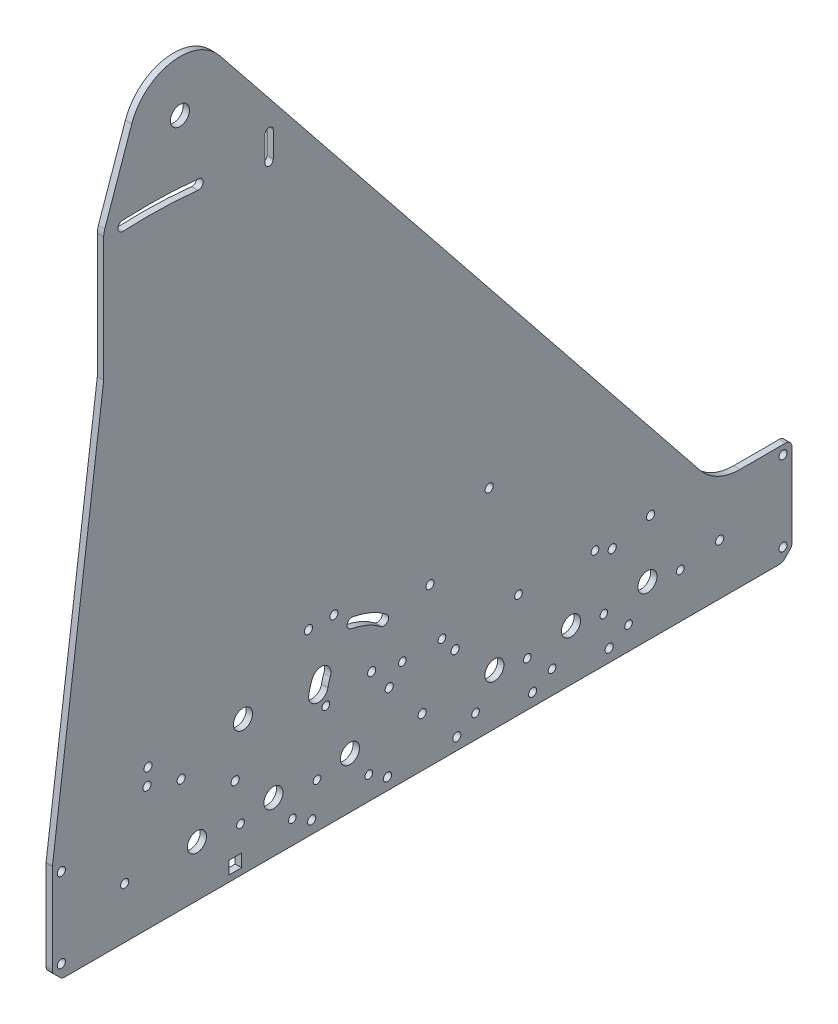
SolidWorks part; units mm, degrees
ref_plane "Front Plane" through (0, 0, 0) normal (0, 0, 1) x (1, 0, 0)
ref_plane "Top Plane" through (0, 0, 0) normal (0, 1, 0) x (1, 0, 0)
ref_plane "Right Plane" through (0, 0, 0) normal (1, 0, 0) x (0, 0, -1)
sketch "Sketch1" plane through (0, 0, 0) normal (1, 0, 0) x (0, 0, -1)
  line L0 (-184.15, -24.6062) -> (184.15, -24.6062)
  line L1 (184.15, -24.6062) -> (184.15, 26.1938)
  line L2 (184.15, 26.1938) -> (146.05, 26.1937)
  line L5 (-145.839, 321.5609) -> (-184.15, 26.1938)
  line L6 (-184.15, 26.1938) -> (-184.15, -24.6062)
  line L7 (-184.15, 350.0437) -> (184.15, 350.0437) construction
  line L9 (146.05, 26.1937) -> (-100.8314, 334.1803)
  arc A0 (-100.8314, 334.1803) -> (-145.839, 321.5609) centre (-120.65, 318.2937) ccw
  point P8 (0, -24.6062)
  dimension "D1" = 368.3
  dimension "D7" = 25.4
  dimension "D2" = 50.8
  dimension "D3" = 38.1
  dimension "D4" = 24.6062
  dimension "D5" = 374.65
  dimension "D6" = 304.8
  dimension "D8" = 342.9
extrude "Boss-Extrude1" add sketch "Sketch1" along normal blind 3.175
chamfer "Chamfer1" distance 4.7625 angle 45 2 edges at (1.5875, -24.6062, 184.15) (1.5875, -24.6062, -184.15)
fillet "Fillet1" radius 25.4 1 edges at (1.5875, 26.1937, -146.05)
fillet "Fillet2" radius 3.175 2 edges at (1.5875, 26.1938, 184.15) (1.5875, 26.1938, -184.15)
fillet "Fillet3" radius 3.175 4 edges at (1.5875, -19.8438, -184.15) (1.5875, -24.6062, -179.3875) (1.5875, -19.8437, 184.15) (1.5875, -24.6062, 179.3875)
sketch "Sketch30" plane through (3.175, 0, 0) normal (1, 0, 0) x (0, 0, -1)
  circle A8 centre (-89.211, 42.2593) radius 4.7625
  circle A9 centre (-25.1593, 30.6938) radius 2.032
  arc A10 (-51.7173, 35.4892) -> (-50.2741, 40.5715) centre (-25.1593, 30.6938) cw construction
  arc A11 (-54.7652, 42.3379) -> (-56.4665, 36.3468) centre (-25.1593, 30.6938) ccw
  arc A12 (-45.783, 38.8051) -> (-46.9681, 34.6317) centre (-25.1593, 30.6938) ccw
  arc A13 (-45.783, 38.8051) -> (-54.7652, 42.3379) centre (-50.2741, 40.5715) ccw
  arc A14 (-56.4665, 36.3468) -> (-46.9681, 34.6317) centre (-51.7173, 35.4892) ccw
  arc A15 (-34.9881, 56.6661) -> (-19.1131, 49.8125) centre (-41.7582, 19.1724) cw construction
  arc A16 (-17.6789, 51.753) -> (-34.5594, 59.0407) centre (-41.7582, 19.1724) ccw
  arc A17 (-20.5473, 47.8719) -> (-35.4169, 54.2915) centre (-41.7582, 19.1724) ccw
  arc A18 (-20.5473, 47.8719) -> (-17.6789, 51.753) centre (-19.1131, 49.8125) ccw
  arc A19 (-34.5594, 59.0407) -> (-35.4169, 54.2915) centre (-34.9881, 56.6661) ccw
  arc A20 (-19.1131, 49.8125) -> (-34.9881, 56.6661) centre (-41.7582, 19.1724) ccw construction
  circle A21 centre (94.6345, 23.8125) radius 2.032
  circle A22 centre (-56.6241, 64.5541) radius 2.032
  circle A23 centre (-43.9241, 64.5541) radius 2.032
  circle A24 centre (-56.6241, 64.5541) radius 1.905 construction
  circle A25 centre (-43.9241, 64.5541) radius 1.905 construction
  point P7 (-51.1204, 38.0658)
  point P19 (-26.6567, 54.1518)
  dimension "D2" = 9.652
  dimension "D4" = 4.064
  dimension "D1" = 4.064
  dimension ".375" = 9.525
  dimension "D3" = 4.826
extrude "Cut-Extrude9" cut sketch "Sketch30" against normal through all
sketch "Sketch16" plane through (3.175, 0, 0) normal (1, 0, 0) x (0, 0, -1)
  circle A0 centre (112.1746, 0.7937) radius 4.7625
  circle A1 centre (74.0746, 0.7937) radius 4.7625
  circle A2 centre (35.9746, 0.7937) radius 4.7625
  circle A3 centre (-35.9746, 0.7938) radius 4.7625
  circle A4 centre (-74.0746, 0.7938) radius 4.7625
  circle A5 centre (-112.1746, 0.7937) radius 4.7625
  dimension "D1" = 9.525
  dimension "D2" = 9.525
extrude "Cut-Extrude1" cut sketch "Sketch16" against normal up to next
sketch "Sketch25" plane through (3.175, 0, 0) normal (1, 0, 0) x (0, 0, -1)
  circle A0 centre (102.7672, -13.0003) radius 1.905 construction
  circle A1 centre (86.0486, 27.3622) radius 1.905 construction
  circle A2 centre (128.5804, -2.3081) radius 1.905 construction
  circle A3 centre (102.7672, -13.0003) radius 1.905
  circle A4 centre (86.0486, 27.3622) radius 1.905
  circle A5 centre (128.5804, -2.3081) radius 1.905
  circle A6 centre (64.6672, -13.0003) radius 1.905 construction
  circle A8 centre (-9.8486, 27.3622) radius 1.905 construction
  circle A10 centre (-47.9486, 27.3622) radius 1.905 construction
  circle A11 centre (-90.4804, -2.3081) radius 1.905 construction
  circle A12 centre (-64.6672, -13.0003) radius 1.905 construction
  circle A14 centre (-52.3804, -2.3081) radius 1.905 construction
  circle A15 centre (-26.5672, -13.0003) radius 1.905 construction
  circle A16 centre (9.8486, 27.3622) radius 1.905 construction
  circle A17 centre (26.5672, -13.0003) radius 1.905 construction
  circle A18 centre (47.9486, 27.3622) radius 1.905 construction
  circle A19 centre (52.3804, -2.3081) radius 1.905 construction
  circle A20 centre (90.4804, -2.3081) radius 1.905 construction
  circle A21 centre (-9.8486, 27.3622) radius 1.905
  circle A23 centre (-47.9486, 27.3622) radius 1.905
  circle A24 centre (-90.4804, -2.3081) radius 1.905
  circle A25 centre (-64.6672, -13.0003) radius 1.905
  circle A27 centre (-52.3804, -2.3081) radius 1.905
  circle A28 centre (-26.5672, -13.0003) radius 1.905
  circle A29 centre (9.8486, 27.3622) radius 1.905
  circle A30 centre (26.5672, -13.0003) radius 1.905
  circle A31 centre (47.9486, 27.3622) radius 1.905
  circle A32 centre (64.6672, -13.0003) radius 1.905
  circle A33 centre (52.3804, -2.3081) radius 1.905
  circle A34 centre (90.4804, -2.3081) radius 1.905
extrude "Cut-Extrude4" cut sketch "Sketch25" against normal up to next
sketch "Sketch23" plane through (3.175, 0, 0) normal (1, 0, 0) x (0, 0, -1)
  circle A0 centre (179.705, 21.7488) radius 1.905 construction
  point P0 (-55.0246, -18.3223)
  point P6 (-93.1246, 17.5943)
  point P9 (-17.2515, -18.6426)
  point P12 (-16.4124, 19.3854)
  point P15 (16.4124, 19.3854)
  point P18 (17.2515, -18.6426)
  point P21 (55.0246, -18.3223)
  point P35 (3.8736, 53.6853)
  point P38 (113.7728, 28.6594)
  point P41 (-137.0088, 37.226)
  point P44 (-179.705, 21.7487)
  point P47 (-179.705, -18.0026)
  point P50 (179.705, 21.7488)
  point P53 (179.705, -18.0026)
  point P59 (93.1246, -18.3223)
hole_wizard "#8 (0.16) Diameter Hole1" positions "Sketch23" profile "Sketch24" hole size "#8" standard "ANSI Inch" end condition up to next
sketch "Sketch24" plane through (3.175, -18.3223, 55.0246) normal (0, 1, 0) x (0, 0, -1)
  line L0 (0, 0) -> (0, 3.175)
  line L1 (0, 3.175) -> (2.032, 3.175)
  line L2 (2.032, 3.175) -> (2.032, 0)
  line L5 (2.032, 0) -> (0, 0)
  line L11 (0, -6.35) -> (0, 107.95) construction
  dimension "Thru Hole Dia." = 4.064
  dimension "Thru Hole Depth" = 3.175
sketch "Sketch22" plane through (3.175, 0, 0) normal (1, 0, 0) x (0, 0, -1)
  line L0 (-96.2996, -15.1473) -> (-89.9496, -15.1473) construction
  line L1 (-96.2996, -15.1473) -> (-89.9496, -15.1473)
  line L2 (-96.2996, -15.1473) -> (-96.2996, -21.4973)
  line L3 (-96.2996, -21.4973) -> (-89.9496, -21.4973)
  line L4 (-89.9496, -15.1473) -> (-89.9496, -21.4973)
  line L5 (-96.2996, -15.1473) -> (-89.9496, -21.4973) construction
  line L6 (-96.2996, -21.4973) -> (-89.9496, -15.1473) construction
  line L7 (-89.9496, -15.1473) -> (-89.9496, -19.8734) construction
  point P0 (-93.1246, -18.3223)
  dimension "D1" = 6.35
extrude "Cut-Extrude3" cut sketch "Sketch22" against normal up to next
sketch "Sketch21" plane through (3.175, 0, 0) normal (1, 0, 0) x (0, 0, -1)
  circle A0 centre (-148.1579, 0.7937) radius 2.032
  circle A2 centre (0, 0) radius 2.032
  circle A3 centre (148.1579, 0.7938) radius 2.032
  dimension "D1" = 4.064
extrude "Cut-Extrude2" cut sketch "Sketch21" against normal up to next
sketch "Sketch26" [suppressed] plane through (3.175, 0, 0) normal (1, 0, 0) x (0, 0, -1)
  line L0 (-145.839, 321.5609) -> (-184.1236, 26.3971) construction
  line L1 (-178.0724, -24.6062) -> (178.0724, -24.6062) construction
  circle A0 centre (-121.0218, 216.6937) radius 15.24
  dimension "D1" = 30.48
  dimension "D2" = 38.1
  dimension "D3" = 241.3
extrude "Cut-Extrude5" [suppressed] cut sketch "Sketch26" against normal through all
sketch "Sketch27" plane through (3.175, 0, 0) normal (1, 0, 0) x (0, 0, -1)
  circle A0 centre (-120.65, 318.2937) radius 4.7625
  dimension "D1" = 9.525
extrude "Cut-Extrude6" cut sketch "Sketch27" against normal through all
sketch "Sketch28" plane through (3.175, 0, 0) normal (1, 0, 0) x (0, 0, -1)
  line L0 (-120.65, 318.2937) -> (-103.5612, 277.2599) construction
  line L1 (-103.5612, 277.2599) -> (-86.3654, 258.566) construction
  line L2 (-86.3654, 258.566) -> (-90.1612, 246.4465) construction
  line L3 (-90.1612, 246.4465) -> (-93.9569, 234.327) construction
  line L4 (-145.839, 321.5609) -> (-184.1236, 26.3971) construction
  circle A0 centre (-93.9569, 234.327) radius 2.032
  circle A1 centre (-90.1612, 246.4465) radius 2.032
  circle A2 centre (-86.3654, 258.566) radius 2.0955
  circle A3 centre (-103.5612, 277.2599) radius 2.032
  dimension "D4" = 4.064
  dimension "D5" = 4.191
  dimension "D6" = 4.064
  dimension "D1" = 25.4
  dimension "D2" = 44.45
  dimension "D3" = 12.7
  dimension "D7" = 30
  dimension "D8" = 120
  dimension "D9" = 160
extrude "Cut-Extrude7" [suppressed] cut sketch "Sketch28" against normal through all
sketch "Sketch29" plane through (3.175, 0, 0) normal (1, 0, 0) x (0, 0, -1)
  line L1 (-76.2, 288.925) -> (-76.2, 276.225) construction
  line L2 (-74.168, 288.925) -> (-74.168, 276.225)
  line L3 (-78.232, 288.925) -> (-78.232, 276.225)
  arc A4 (-74.168, 288.925) -> (-78.232, 288.925) centre (-76.2, 288.925) ccw
  arc A5 (-78.232, 276.225) -> (-74.168, 276.225) centre (-76.2, 276.225) ccw
  point P8 (-76.2, 282.575)
  dimension "D1" = 276.225
  dimension "D2" = 2.032
  dimension "D3" = 76.2
  dimension "D4" = 12.7
sketch "Sketch31" plane through (0, 0, 0) normal (-1, 0, 0) x (0, 0, 1)
extrude "Cut-Extrude10" [suppressed] cut sketch "Sketch31" against normal through all
sketch "Sketch34" plane through (0, 0, 0) normal (-1, 0, 0) x (0, 0, 1)
  line L3 (123.9045, 95.7355) -> (127.1716, 70.5465) construction
  line L4 (126.0455, 96.0132) -> (129.3127, 70.8242)
  line L5 (121.7634, 95.4578) -> (125.0306, 70.2688)
  line L6 (145.839, 321.5609) -> (184.1236, 26.3971) construction
  arc A2 (126.0455, 96.0132) -> (121.7634, 95.4578) centre (123.9045, 95.7355) ccw
  arc A3 (125.0306, 70.2688) -> (129.3127, 70.8242) centre (127.1716, 70.5465) ccw
  point P9 (125.538, 83.141)
  dimension "D8" = 4.318
  dimension "D6" = 50.8
  dimension "D7" = 25.4
extrude "Cut-Extrude12" [suppressed] cut sketch "Sketch34" against normal through all
sketch "Sketch38" plane through (3.175, 0, 0) normal (1, 0, 0) x (0, 0, -1)
  line L0 (-184.15, 25.9887) -> (-184.15, -18.5286) construction
  line L1 (-178.0724, -24.6062) -> (178.0724, -24.6062) construction
  circle A0 centre (-136.525, 45.2437) radius 2.032
  dimension "D1" = 47.625
  dimension "D3" = 4.064
  dimension "D2" = 69.85
extrude "Cut-Extrude14" cut sketch "Sketch38" against normal through all
sketch "Sketch37" plane through (3.175, 0, 0) normal (1, 0, 0) x (0, 0, -1)
  circle A0 centre (33.3375, 80.645) radius 2.032
  circle A8 centre (0, 0) radius 2.032 construction
  dimension "D1" = 4.064
  dimension "D2" = 33.3375
  dimension "D3" = 80.645
extrude "Cut-Extrude13" cut sketch "Sketch37" against normal through all
extrude "Cut-Extrude15" cut sketch "Sketch29" against normal through all
sketch "Sketch40" plane through (3.175, 0, 0) normal (1, 0, 0) x (0, 0, -1)
  circle A0 centre (-120.015, 31.75) radius 2.032
  dimension "D1" = 4.064
  dimension "D2" = 120.015
  dimension "D3" = 31.75
extrude "Cut-Extrude16" cut sketch "Sketch40" against normal through all
sketch "Sketch41" [suppressed] plane through (3.175, 0, 0) normal (1, 0, 0) x (0, 0, -1)
  line L0 (-120.65, 318.2937) -> (-98.425, 279.7989) construction
  line L1 (-98.425, 279.7989) -> (-77.6666, 265.1617) construction
  line L2 (-120.65, 318.2937) -> (-60.41, 318.2937) construction
  circle A0 centre (-120.65, 318.2937) radius 25.4 construction
  circle A1 centre (-98.425, 279.7989) radius 19.05 construction
  circle A2 centre (-77.6666, 265.1617) radius 6.35 construction
  circle A3 centre (-98.425, 279.7989) radius 2.032
  circle A4 centre (-77.6666, 265.1617) radius 2.032
  dimension "D1" = 50.8
  dimension "D2" = 38.1
  dimension "D3" = 12.7
  dimension "D4" = 4.064
  dimension "D5" = 60
extrude "Cut-Extrude17" [suppressed] cut sketch "Sketch41" against normal through all
sketch "Sketch43" plane through (3.175, 0, 0) normal (1, 0, 0) x (0, 0, -1)
  line L0 (-152.4, 200.025) -> (-123.6487, 200.025) construction
  line L1 (-115.9779, 252.0412) -> (-152.4, 200.025) construction
  circle A0 centre (-152.4, 200.025) radius 2.032
  arc A1 (-143.2813, 262.8669) -> (-96.4668, 230.087) centre (-152.4, 200.025) cw construction
  arc A2 (-92.2158, 232.3717) -> (-142.5883, 267.6428) centre (-152.4, 200.025) ccw
  arc A3 (-100.7177, 227.8023) -> (-143.9743, 258.0909) centre (-152.4, 200.025) ccw
  arc A4 (-100.7177, 227.8023) -> (-92.2158, 232.3717) centre (-96.4668, 230.087) ccw
  arc A5 (-142.5883, 267.6428) -> (-143.9743, 258.0909) centre (-143.2813, 262.8669) ccw
  point P6 (-115.9779, 252.0412)
  dimension "D1" = 4.064
  dimension "D4" = 4.826
  dimension "D2" = 200.025
  dimension "D3" = 152.4
  dimension "D5" = 63.5
  dimension "D6" = 57.15
  dimension "D7" = 55
extrude "Cut-Extrude19" [suppressed] cut sketch "Sketch43" against normal through all
sketch "Sketch44" plane through (3.175, 0, 0) normal (1, 0, 0) x (0, 0, -1)
  circle A0 centre (-142.875, 226.3775) radius 2.032
  dimension "D1" = 4.064
  dimension "D2" = 142.875
  dimension "D3" = 226.3775
extrude "Cut-Extrude20" [suppressed] cut sketch "Sketch44" against normal through all
sketch "Sketch50" plane through (0, 0, 0) normal (-1, 0, 0) x (0, 0, 1)
  line L0 (89.6567, 207.1688) -> (64.2567, 207.1688) construction
  line L1 (89.6567, 205.1368) -> (64.2567, 205.1368)
  line L2 (89.6567, 209.2008) -> (64.2567, 209.2008)
  line L3 (64.2567, 194.4688) -> (38.8567, 194.4688) construction
  line L4 (64.2567, 192.4368) -> (38.8567, 192.4368)
  line L5 (64.2567, 196.5008) -> (38.8567, 196.5008)
  arc A1 (89.6567, 205.1368) -> (89.6567, 209.2008) centre (89.6567, 207.1688) ccw
  arc A2 (64.2567, 209.2008) -> (64.2567, 205.1368) centre (64.2567, 207.1688) ccw
  arc A3 (64.2567, 192.4368) -> (64.2567, 196.5008) centre (64.2567, 194.4688) ccw
  arc A4 (38.8567, 196.5008) -> (38.8567, 192.4368) centre (38.8567, 194.4688) ccw
  point P3 (76.9567, 207.1688)
  point P5 (51.5567, 194.4688)
  dimension "D1" = 2.032
  dimension "D2" = 207.1688
  dimension "D3" = 89.6567
  dimension "D4" = 25.4
  dimension "D5" = 12.7
extrude "Cut-Extrude22" [suppressed] cut sketch "Sketch50" against normal through all
sketch "Sketch51" plane through (3.175, 0, 0) normal (1, 0, 0) x (0, 0, -1)
  circle A0 centre (-111.125, 222.6469) radius 2.032
  circle A1 centre (-111.125, 190.8969) radius 2.032
  dimension "D1" = 222.6469
  dimension "D3" = 31.75
  dimension "D4" = 4.064
  dimension "D2" = 111.125
extrude "Cut-Extrude23" [suppressed] cut sketch "Sketch51" against normal through all
sketch "Sketch52" [suppressed] plane through (0, 0, 0) normal (-1, 0, 0) x (0, 0, 1)
  line L0 (145.839, 321.5609) -> (184.1236, 26.3971) construction
  line L1 (142.875, 226.3775) -> (142.0856, 251.7652) construction
  line L2 (120.4939, 238.3877) -> (142.875, 226.3775) construction
  arc A5 (142.0856, 251.7652) -> (120.4939, 238.3877) centre (142.875, 226.3775) ccw construction
  arc A6 (142.0224, 253.7962) -> (118.7034, 239.3485) centre (142.875, 226.3775) ccw
  arc A7 (142.1487, 249.7342) -> (122.2844, 237.4269) centre (142.875, 226.3775) ccw
  arc A8 (142.1487, 249.7342) -> (142.0224, 253.7962) centre (142.0856, 251.7652) ccw
  arc A9 (118.7034, 239.3485) -> (122.2844, 237.4269) centre (120.4939, 238.3877) ccw
  point P4 (129.4975, 247.9692)
  dimension "D1" = 25.4
  dimension "D2" = 2.032
  dimension "D3" = 12.7
  dimension "D4" = 60
extrude "Cut-Extrude24" [suppressed] cut sketch "Sketch52" against normal through all
sketch "Sketch53" plane through (3.175, 0, 0) normal (1, 0, 0) x (0, 0, -1)
  line L0 (-25.4, 197.2663) -> (-25.4, 135.876) construction
  line L1 (-23.368, 197.2663) -> (-23.368, 135.876)
  line L2 (-27.432, 197.2663) -> (-27.432, 135.876)
  arc A0 (-23.368, 197.2663) -> (-27.432, 197.2663) centre (-25.4, 197.2663) ccw
  arc A1 (-27.432, 135.876) -> (-23.368, 135.876) centre (-25.4, 135.876) ccw
  point P2 (-25.4, 166.5712)
  dimension "D1" = 2.032
  dimension "D2" = 61.3903
  dimension "D3" = 197.2663
  dimension "D4" = 25.4
extrude "Cut-Extrude25" [suppressed] cut sketch "Sketch53" against normal through all
sketch "Sketch56" plane through (3.175, 0, 0) normal (1, 0, 0) x (0, 0, -1)
  line L0 (-136.525, 285.2438) -> (-136.525, 45.2437) construction
  line L1 (-149.0856, 284.9148) -> (-136.525, 45.2437) construction
  line L2 (-136.525, 45.2437) -> (-111.4382, 283.929) construction
  arc A0 (-149.0856, 284.9148) -> (-111.4382, 283.929) centre (-136.525, 45.2437) cw
  dimension "D1" = 3
  dimension "D3" = 240
  dimension "D2" = 6
sketch "Sketch54" plane through (3.175, 0, 0) normal (1, 0, 0) x (0, 0, -1)
  line L0 (-145.839, 321.5609) -> (-184.1236, 26.3971) construction
  line L1 (-144.6368, 326.648) -> (-158.0807, 288.0477)
  line L2 (-145.839, 321.5609) -> (-158.6106, 223.0952)
  line L3 (-144.6368, 326.648) -> (-218.1381, 326.648) construction
  line L5 (-158.6106, 284.9148) -> (-158.6106, 223.0952)
  arc A1 (-100.8314, 334.1803) -> (-145.839, 321.5609) centre (-120.65, 318.2937) ccw construction
  arc A2 (-158.0807, 288.0477) -> (-158.6106, 284.9148) centre (-149.0856, 284.9148) ccw
  arc A3 (-144.6368, 326.648) -> (-145.839, 321.5609) centre (-120.65, 318.2937) ccw
  dimension "D1" = 9.525
extrude "Boss-Extrude2" add sketch "Sketch54" against normal up to surface (3.175 mm away) up to face at (0, 31.75, 117.983)
sketch "Sketch57" plane through (3.175, 0, 0) normal (1, 0, 0) x (0, 0, -1)
  arc A0 (-149.0856, 284.9148) -> (-111.4382, 283.929) centre (-136.525, 45.2437) cw construction
  arc A1 (-111.1859, 286.3288) -> (-149.2119, 287.3245) centre (-136.525, 45.2437) ccw
  arc A2 (-111.6904, 281.5292) -> (-148.9593, 282.5051) centre (-136.525, 45.2437) ccw
  arc A3 (-111.6904, 281.5292) -> (-111.1859, 286.3288) centre (-111.4382, 283.929) ccw
  arc A4 (-149.2119, 287.3245) -> (-148.9593, 282.5051) centre (-149.0856, 284.9148) ccw
  arc A5 (-111.4382, 283.929) -> (-149.0856, 284.9148) centre (-136.525, 45.2437) ccw construction
  point P3 (-130.2425, 285.1615)
  dimension "D1" = 4.826
extrude "Cut-Extrude26" cut sketch "Sketch57" against normal up to next
